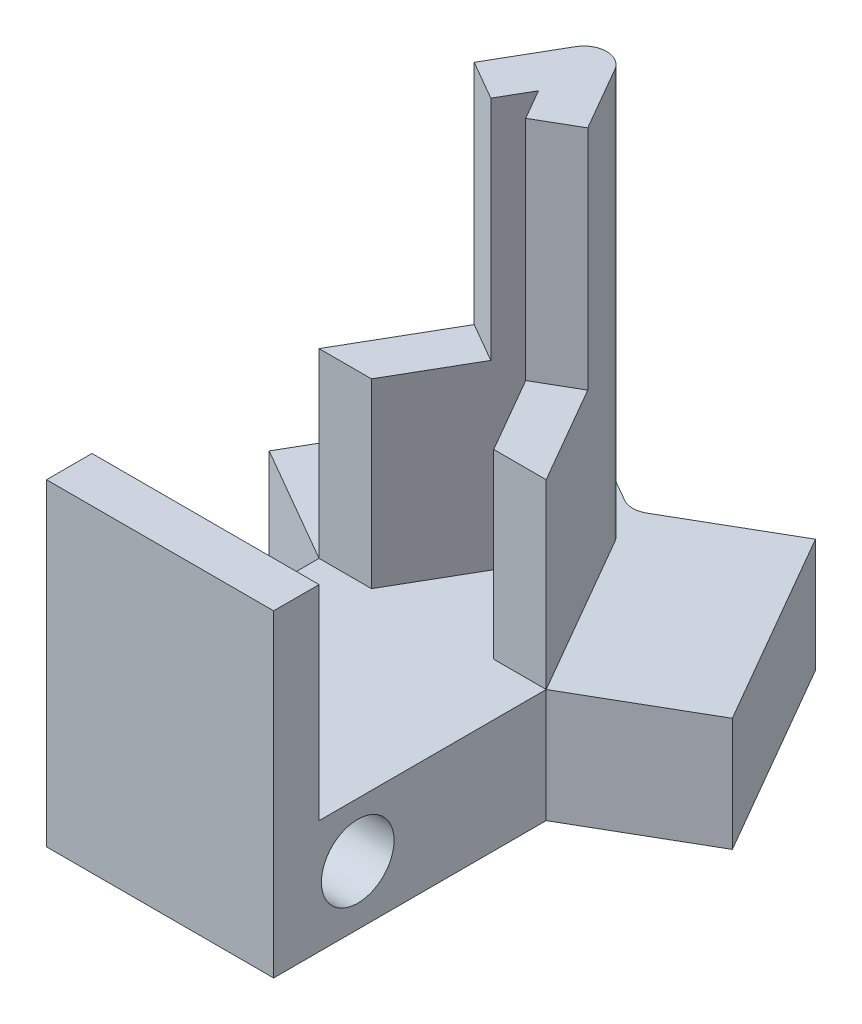
SolidWorks part; units mm, degrees
ref_plane "Front Plane" through (0, 0, 0) normal (0, 0, 1) x (1, 0, 0)
ref_plane "Top Plane" through (0, 0, 0) normal (0, 1, 0) x (1, 0, 0)
ref_plane "Right Plane" through (0, 0, 0) normal (1, 0, 0) x (0, 0, -1)
sketch "Sketch3" plane through (0, 0, 0) normal (0, 1, 0) x (1, 0, 0)
  line L0 (-16.282, 0) -> (-6.282, 0)
  line L3 (-11.282, 8.6603) -> (-16.4781, 11.6603)
  line L4 (-16.4781, 11.6603) -> (-21.4781, 3)
  line L5 (-21.4781, 3) -> (-16.282, 0)
  line L7 (-11.282, 8.6603) -> (-6.0858, 11.6603)
  line L8 (-6.0858, 11.6603) -> (-1.0858, 3)
  line L9 (-1.0858, 3) -> (-6.282, 0)
  dimension "D3" = 10
  dimension "D4" = 6
  dimension "D5" = 6
  dimension "D9" = 6
  dimension "D10" = 6
  dimension "D11" = 10
extrude "Boss-Extrude1" add sketch "Sketch3" along normal blind 2 and the other way blind 3
sketch "Sketch7" plane through (0, 2, 0) normal (0, 1, 0) x (1, 0, 0)
  line L0 (-11.282, 8.6603) -> (-16.282, 0)
  line L1 (-16.282, 0) -> (-13.9726, 0)
  line L2 (-6.282, 0) -> (-11.282, 8.6603)
  line L3 (-11.282, 4.6603) -> (-12.8179, 2)
  line L4 (-12.8179, 2) -> (-13.9726, 0)
  line L5 (-9.7461, 2) -> (-11.282, 4.6603)
  line L6 (-12.8179, 2) -> (-9.7461, 2) construction
  line L7 (-13.9726, 0) -> (-11.282, 4.6603)
  line L8 (-9.7461, 2) -> (-8.5914, 0)
  line L9 (-8.5914, 0) -> (-6.282, 0)
  line L10 (-16.282, 0) -> (-6.282, 0) construction
  line M4 (-16.282, 0) -> (-6.282, 0)
  dimension "D1" = 2
extrude "Boss-Extrude2" add sketch "Sketch7" along normal blind 18 contours L5 L8 L2 L0 L4 L3 M4 region at (-8.8966, 2, -4.264)
sketch "Sketch8" plane through (0, 0, 0) normal (0, 1, 0) x (1, 0, 0)
  line L0 (-16.282, 0) -> (-16.282, -12)
  line L1 (-16.282, -12) -> (-6.282, -12)
  line L2 (-6.282, -12) -> (-6.282, 0)
  line L3 (-16.282, 0) -> (-6.282, 0)
  dimension "D1" = 12
  dimension "D2" = 90
extrude "Boss-Extrude3" add sketch "Sketch8" along normal blind 2 and the other way blind 3
sketch "Sketch9" plane through (0, 2, 0) normal (0, 1, 0) x (1, 0, 0)
  line L0 (-16.282, -12) -> (-16.282, -9.998)
  line L1 (-16.282, 0) -> (-16.282, -12) construction
  line L2 (-16.282, -9.998) -> (-6.282, -9.998)
  line L3 (-6.282, -12) -> (-6.282, 0) construction
  line L4 (-6.282, -9.998) -> (-6.282, -12)
  line L5 (-6.282, -12) -> (-16.282, -12)
extrude "Boss-Extrude4" add sketch "Sketch9" along normal blind 18
sketch "Sketch10" plane through (0, 20, 0) normal (0, 1, 0) x (1, 0, 0)
  line L0 (-16.282, 0) -> (-13.782, 4.3301)
  line L1 (-11.282, 8.6603) -> (-16.282, 0) construction
  line L2 (-13.782, 4.3301) -> (-12.0499, 3.3301)
  line L3 (-11.282, 4.6603) -> (-13.9726, 0) construction
  line L4 (-12.0499, 3.3301) -> (-13.9726, 0)
  line L5 (-13.9726, 0) -> (-16.282, 0)
  line L6 (-6.282, 0) -> (-8.782, 4.3301)
  line L7 (-6.282, 0) -> (-11.282, 8.6603) construction
  line L8 (-8.782, 4.3301) -> (-10.514, 3.3301)
  line L9 (-8.5914, 0) -> (-11.282, 4.6603) construction
  line L10 (-10.514, 3.3301) -> (-8.5914, 0)
  line L11 (-8.5914, 0) -> (-6.282, 0)
  line L12 (-6.282, 0) -> (-6.2968, -0.0584)
  line M1 (-11.282, 4.6603) -> (-8.5914, 0)
  line M2 (-8.5914, 0) -> (-6.282, 0)
  line M3 (-6.282, 0) -> (-11.282, 8.6603)
  line M4 (-11.282, 8.6603) -> (-16.282, 0)
  line M5 (-16.282, 0) -> (-13.9726, 0)
  line M6 (-13.9726, 0) -> (-11.282, 4.6603)
extrude "Cut-Extrude1" cut sketch "Sketch10" against normal blind 10 contours L2 M4 M5 M6 | L8 M3 M1 M2 region at (-14.0656, 20, -1.9259) region at (-8.4984, 20, -1.9259)
sketch "Sketch12" plane through (0, 0, 12) normal (0, 0, 1) x (1, 0, 0)
  line L0 (-16.282, 20) -> (-16.282, 11)
  line L1 (-16.282, 20) -> (-16.282, -3) construction
  line L2 (-16.282, 11) -> (-6.282, 11)
  line L3 (-6.282, 20) -> (-6.282, -3) construction
  line L4 (-6.282, 11) -> (-6.282, 20)
  line L5 (-6.282, 20) -> (-16.282, 20)
  dimension "D1" = 9
  dimension "D2" = 9
extrude "Cut-Extrude3" cut sketch "Sketch12" against normal blind 3
fillet "Fillet3" radius 1 1 edges at (-11.282, 11, -8.6603)
fillet "Fillet4" radius 1 1 edges at (-11.282, -0.5, -8.6603)
sketch "Sketch14" plane through (-6.282, 0, 0) normal (1, 0, 0) x (0, 0, -1)
  line L0 (-12, -3) -> (0, -3) construction
  circle A0 centre (-8.2986, -0.4) radius 1.6
  dimension "D1" = 2.6
extrude "Cut-Extrude4" cut sketch "Sketch14" against normal blind 3
